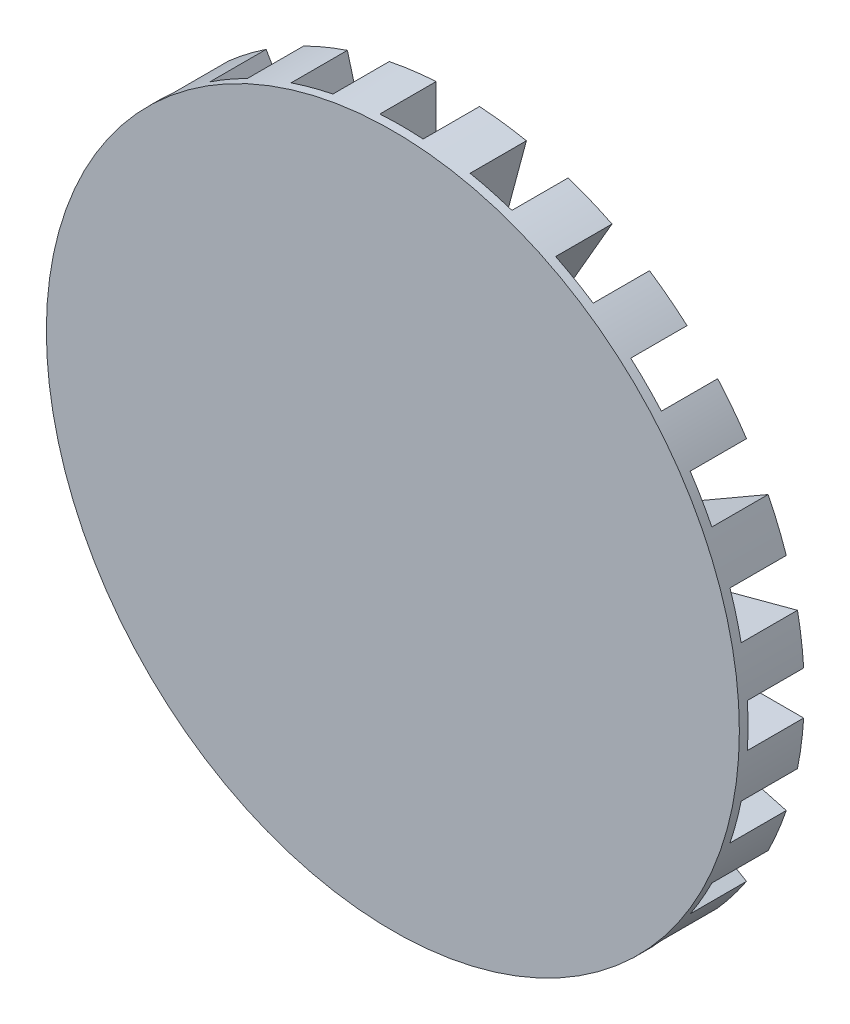
SolidWorks part; units mm, degrees
material "PUR"
ref_plane "Front Plane" through (0, 0, 0) normal (0, 0, 1) x (1, 0, 0)
ref_plane "Top Plane" through (0, 0, 0) normal (0, 1, 0) x (1, 0, 0)
ref_plane "Right Plane" through (0, 0, 0) normal (1, 0, 0) x (0, 0, -1)
sketch "Sketch1" plane through (0, 0, 0) normal (0, 0, 1) x (1, 0, 0)
  circle A0 centre (0, 0) radius 80
  circle A1 centre (0, 0) radius 100 construction
  circle A4 centre (0, 0) radius 100 construction
  dimension "D1" = 20
extrude "Boss-Extrude1" add sketch "Sketch1" along normal blind 2 from offset 13
sketch "Sketch3" plane through (0, 0, 15) normal (0, 0, 1) x (1, 0, 0)
  line L0 (0, 0) -> (0, -80) construction
  line L1 (0, 0) -> (-20.7055, -77.2741) construction
  line L2 (-5, -79.8436) -> (-5, -37.9788)
  line L3 (-5, -37.9788) -> (-15.8354, -78.4171)
  line L4 (-5, -58.9112) -> (0, -58.9112) construction
  line L5 (-10.4177, -58.1979) -> (-15.2473, -56.9038) construction
  circle A0 centre (0, 0) radius 80 construction
  arc A1 (-5, -79.8436) -> (-15.8354, -78.4171) centre (0, 0) cw
  dimension "D1" = 10
  dimension "D2" = 15
extrude "Boss-Extrude2" add sketch "Sketch3" against normal up to surface (15 mm away)
pattern_circular "CirPattern1" count 24 over 360 about axis through (0, 0, 15) along (0, 0, -1) of "Boss-Extrude2"
sketch "Sketch4" plane through (0, 0, 0) normal (0, 0, -1) x (-1, 0, 0)
  line L0 (-10.4421, 79.3156) -> (0, 0) construction
  line L1 (0, 0) -> (0, 80) construction
  circle A0 centre (-9.7895, 74.3584) radius 1
  arc A1 (-5, 79.8436) -> (-15.8354, 78.4171) centre (0, 0) ccw construction
  arc A2 (5, 79.8436) -> (-5, 79.8436) centre (0, 0) ccw construction
  dimension "D2" = 2
  dimension "D1" = 75
extrude "Cut-Extrude1" cut sketch "Sketch4" against normal blind 8
pattern_circular "CirPattern2" count 12 over 360 about axis through (0, 0, 15) along (0, 0, 1) of "Cut-Extrude1"
